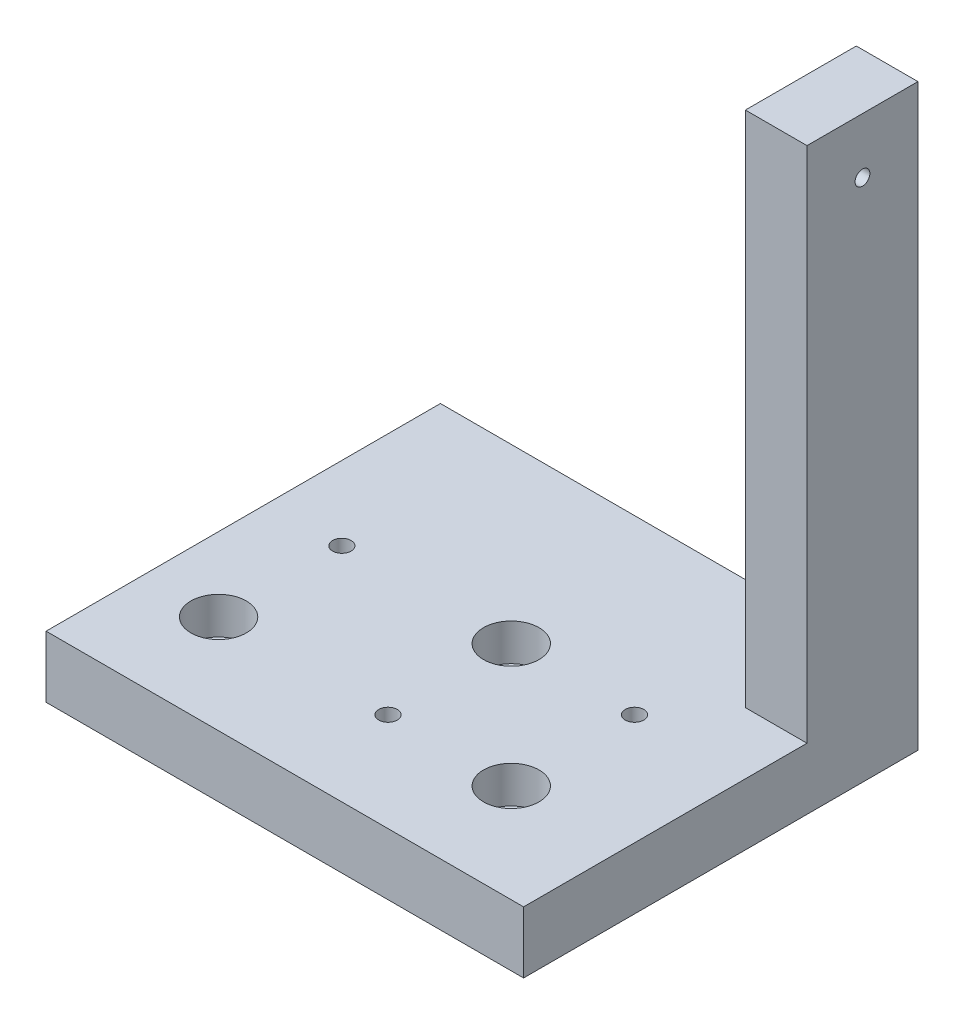
SolidWorks part; units mm, degrees
ref_plane "前视基准面" through (0, 0, 0) normal (0, 0, 1) x (1, 0, 0)
ref_plane "上视基准面" through (0, 0, 0) normal (0, 1, 0) x (1, 0, 0)
ref_plane "右视基准面" through (0, 0, 0) normal (1, 0, 0) x (0, 0, -1)
other "Configuration Table"
sketch "草图1" plane through (0, 0, 0) normal (0, 1, 0) x (1, 0, 0)
  line L1 (0, 0) -> (-38.75, 0)
  line L2 (0, 0) -> (0, 30)
  line L3 (0, 30) -> (-38.75, 30)
  line L4 (-38.75, 0) -> (-38.75, 30)
  line L5 (0, 30) -> (-5, 30)
  line L6 (0, 30) -> (0, 25)
  line L7 (0, 25) -> (-5, 25)
  line L8 (-5, 30) -> (-5, 25)
  dimension "D1" = 30
  dimension "D2" = 38.75
  dimension "D3" = 5
extrude "凸台-拉伸1" add sketch "草图1" along normal blind 5 contours L3 L4 L1 L2
extrude "凸台-拉伸2" add sketch "草图1<15>" along normal blind 47 contours L6 L7 L8 L5
sketch "草图1<15>" plane through (0, 0, 0) normal (0, 1, 0) x (1, 0, 0) same geometry as "草图1"
sketch "草图2" plane through (-5, 0, 0) normal (-1, 0, 0) x (0, 0, 1)
  line L0 (-30, 47) -> (-25, 47) construction
  line L2 (0, 5) -> (-30, 5) construction
  circle A0 centre (-27.5, 42.5) radius 0.6
  point P5 (-27.5, 47)
  dimension "D1" = 1.2
  dimension "D2" = 37.5
extrude "切除-拉伸1" cut sketch "草图2" against normal through all
sketch "草图3" plane through (0, 5, 0) normal (0, 1, 0) x (1, 0, 0)
  line L1 (0, 0) -> (-38.75, 0) construction
  line L2 (0, 0) -> (0, 25) construction
  circle A0 centre (-9, 8) radius 1.5
  circle A1 centre (-32.75, 8) radius 1.5
  circle A2 centre (-19, 18) radius 1.5
  circle A3 centre (-19, 18) radius 2.25
  circle A4 centre (-32.75, 8) radius 2.25
  circle A5 centre (-9, 8) radius 2.25
  circle A6 centre (-32.75, 18) radius 0.75
  circle A7 centre (-9, 18) radius 0.75
  circle A8 centre (-19, 8) radius 0.75
  point P15 (-23.7894, 21.6238)
  point P16 (-19, 8)
  point P17 (-32.75, 18)
  point P19 (-7, 18)
  point P22 (0, 0)
  point P23 (0, 0)
  point P24 (0, 0)
  point P25 (0, 0)
  point P26 (0, 0)
  dimension "D1" = 3
  dimension "D2" = 4.5
  dimension "D3" = 1.5
  dimension "D4" = 8
  dimension "D5" = 9
extrude "切除-拉伸2" cut sketch "草图3" against normal through all contours A1 | A2 | A0 | A6 | A8 | A7
extrude "切除-拉伸3" cut sketch "草图3<3>" against normal offset from surface (3 mm away) 2 contours A4 | A3 | A5 up to face at (-19, 0, -7.25)
sketch "草图3<3>" plane through (0, 5, 0) normal (0, 1, 0) x (1, 0, 0) same geometry as "草图3"
sketch "草图4" plane through (0, 0, -25) normal (0, 0, 1) x (1, 0, 0)
  line L0 (0, 5) -> (-38.75, 5) construction
  line L1 (0, 47) -> (-5, 47)
  line L2 (0, 47) -> (0, 5)
  line L3 (0, 5) -> (-5, 5)
  line L4 (-5, 47) -> (-5, 5)
  line L5 (-5, 47) -> (-5, 5) construction
  line L7 (0, 5) -> (-38.75, 5)
  line L8 (0, 5) -> (0, 0)
  line L9 (0, 0) -> (-38.75, 0)
  line L10 (-38.75, 5) -> (-38.75, 0)
extrude "凸台-拉伸3" add sketch "草图4" along normal blind 2 contours L4 L3 L2 L1
extrude "凸台-拉伸4" add sketch "草图4<3>" against normal blind 2 from surface contours L2 L1 L4 L3 | L7 L10 L9 L8 starting at face at (-14.5833, 17.3333, -30)
sketch "草图4<3>" plane through (0, 0, -25) normal (0, 0, 1) x (1, 0, 0) same geometry as "草图4"
